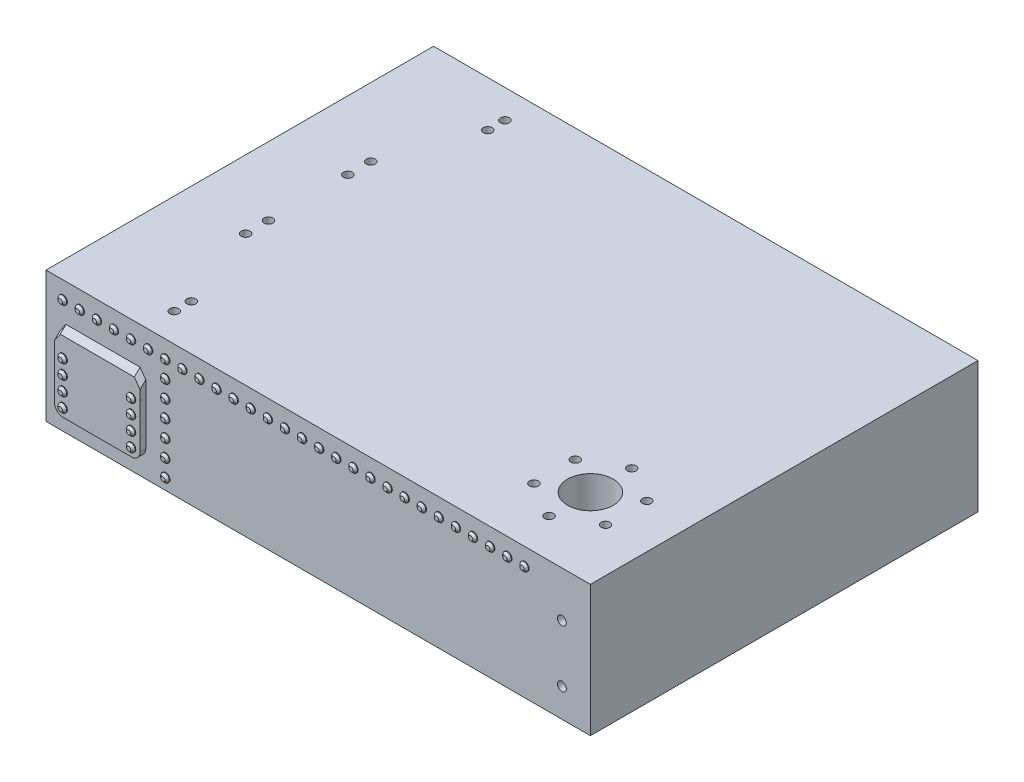
SolidWorks part; units mm, degrees
ref_plane "Front Plane" through (0, 0, 0) normal (0, 0, 1) x (1, 0, 0)
ref_plane "Top Plane" through (0, 0, 0) normal (0, 1, 0) x (1, 0, 0)
ref_plane "Right Plane" through (0, 0, 0) normal (1, 0, 0) x (0, 0, -1)
sketch "Sketch1" plane through (0, 0, 0) normal (0, 1, 0) x (1, 0, 0)
  line L1 (0, 0) -> (191, 0)
  line L2 (0, 0) -> (0, 136)
  line L3 (0, 136) -> (191, 136)
  line L4 (191, 0) -> (191, 136)
  dimension "D1" = 191
  dimension "D2" = 136
extrude "Boss-Extrude1" add sketch "Sketch1" along normal blind 46
sketch "Sketch3" plane through (0, 0, 0) normal (0, -1, 0) x (1, 0, 0)
  line L0 (0, -136) -> (0, 0) construction
  line L1 (5, -5) -> (186, -5)
  line L2 (5, -5) -> (5, -131)
  line L3 (5, -131) -> (186, -131)
  line L4 (186, -5) -> (186, -131)
  line L6 (191, -136) -> (0, -136) construction
  line L7 (191, 0) -> (191, -136) construction
  line L8 (0, 0) -> (191, 0) construction
  dimension "D1" = 5
  dimension "D2" = 5
  dimension "D3" = 5
  dimension "D4" = 5
extrude "Cut-Extrude1" cut sketch "Sketch3" against normal offset from surface (41 mm away) 5 contours L2 L3 L4 L1 up to face at (95.5, 46, -68)
ref_point "FrontLeft"
sketch "Sketch5" plane through (0, 0, -136) normal (0, 0, -1) x (-1, 0, 0)
  line L0 (-191, 46) -> (-119.5, 46)
  line L1 (-191, 46) -> (0, 46) construction
  line L2 (-119.5, 46) -> (-119.5, 0) construction
  line L3 (-191, 0) -> (0, 0) construction
  point P5 (-119.5, 23)
  dimension "D1" = 71.5
sketch "Sketch8" plane through (0, 0, 0) normal (0, 0, 1) x (1, 0, 0)
  line L1 (119.5, 46) -> (119.5, 0) construction
  line L2 (0, 46) -> (191, 46) construction
  line L3 (0, 0) -> (191, 0) construction
  point P0 (119.5, 23)
ref_point "SuspensionMountLeft"
ref_point "SuspensionMountRight"
sketch "Sketch9" plane through (0, 0, -136) normal (0, 0, -1) x (-1, 0, 0)
  line L0 (0, 46) -> (0, 0) construction
  line L1 (-5, 31) -> (-35, 31)
  line L2 (-5, 31) -> (-5, 6.2153)
  line L3 (-5, 6.2153) -> (-35, 6.2153)
  line L4 (-35, 31) -> (-35, 6.2153)
  line L5 (-191, 46) -> (0, 46) construction
  dimension "D1" = 5
  dimension "D2" = 15
  dimension "D3" = 30
extrude "Boss-Extrude2" add sketch "Sketch9" along normal blind 2
chamfer "Chamfer2" distance 2 angle 45 1 edges at (20, 31, -136)
fillet "Fillet1" radius 3 2 edges at (35, 6.2153, -137) (5, 6.2153, -137)
chamfer "Chamfer3" distance 2 angle 45 2 edges at (35, 32, -137) (5, 32, -137)
sketch "Sketch10" plane through (0, 0, 0) normal (0, 0, 1) x (1, 0, 0)
  line L4 (35, 31) -> (5, 31)
  line L5 (35, 6.2153) -> (35, 31)
  line L6 (5, 6.2153) -> (35, 6.2153)
  line L7 (5, 31) -> (5, 6.2153)
  line L8 (35, 31) -> (5, 31)
  line L9 (35, 6.2153) -> (35, 31)
  line L10 (5, 6.2153) -> (35, 6.2153)
  line L11 (5, 31) -> (5, 6.2153)
  dimension "D1" = 0
extrude "Boss-Extrude3" add sketch "Sketch10" along normal blind 2
chamfer "Chamfer4" distance 2 angle 45 1 edges at (20, 31, 0)
fillet "Fillet2" radius 3 2 edges at (35, 6.2153, 1) (5, 6.2153, 1)
chamfer "Chamfer5" distance 2 angle 45 2 edges at (35, 32, 1) (5, 32, 1)
sketch "Sketch23" plane through (0, 0, 2) normal (0, 0, 1) x (1, 0, 0)
  line L0 (8, 9.2153) -> (8, 31) construction
  line L1 (33, 31) -> (7, 31) construction
  line L2 (32, 9.2153) -> (32, 31) construction
  circle A0 centre (8, 9.2153) radius 1.5
  circle A1 centre (32, 9.2153) radius 1.5
  circle A2 centre (8, 14.2153) radius 1.5
  circle A3 centre (32, 14.2153) radius 1.5
  circle A4 centre (8, 19.2153) radius 1.5
  circle A5 centre (32, 19.2153) radius 1.5
  circle A6 centre (8, 24.2153) radius 1.5
  circle A7 centre (32, 24.2153) radius 1.5
  dimension "D1" = 3
  dimension "D2" = 3
  dimension "D3" = 4
extrude "Boss-Extrude8" add sketch "Sketch23" along normal blind 1 contours A4 | A2 | A0 | A1 | A3 | A5 | A7 | A6 region at (8, 9.2153, 2) region at (32, 9.2153, 2) region at (8, 14.2153, 2) region at (32, 14.2153, 2) region at (8, 19.2153, 2) region at (32, 19.2153, 2) region at (32, 24.2153, 2)
chamfer "Chamfer11" distance 0.75 angle 45 8 edges at (9.5, 24.2153, 3) (33.5, 9.2153, 3) (33.5, 14.2153, 3) (33.5, 19.2153, 3) (33.5, 24.2153, 3) (9.5, 9.2153, 3) (9.5, 14.2153, 3) (9.5, 19.2153, 3)
ref_plane "Plane1" through (0, 0, -68) normal (0, 0, 1) x (1, 0, 0)
mirror "Mirror1" about plane through (0, 0, -68) normal (0, 0, 1) of "Chamfer11", "Boss-Extrude8"
sketch "Sketch18" plane through (0, 41, 0) normal (0, -1, 0) x (1, 0, 0)
  line L1 (112.6585, -114) -> (114.6793, -117.5)
  line L2 (114.6793, -117.5) -> (118.7207, -117.5)
  line L3 (118.7207, -117.5) -> (120.7415, -114)
  line L4 (120.7415, -114) -> (118.7207, -110.5)
  line L5 (118.7207, -110.5) -> (114.6793, -110.5)
  line L6 (114.6793, -110.5) -> (112.6585, -114)
  line L7 (112.6585, -66) -> (114.6793, -69.5)
  line L8 (114.6793, -69.5) -> (118.7207, -69.5)
  line L9 (118.7207, -69.5) -> (120.7415, -66)
  line L10 (120.7415, -66) -> (118.7207, -62.5)
  line L11 (118.7207, -62.5) -> (114.6793, -62.5)
  line L12 (114.6793, -62.5) -> (112.6585, -66)
  line L13 (12.4585, -67) -> (14.4793, -70.5)
  line L14 (14.4793, -70.5) -> (18.5207, -70.5)
  line L15 (18.5207, -70.5) -> (20.5415, -67)
  line L16 (20.5415, -67) -> (18.5207, -63.5)
  line L17 (18.5207, -63.5) -> (14.4793, -63.5)
  line L18 (14.4793, -63.5) -> (12.4585, -67)
  line L19 (12.4585, -119.5) -> (14.4793, -123)
  line L20 (14.4793, -123) -> (18.5207, -123)
  line L21 (18.5207, -123) -> (20.5415, -119.5)
  line L22 (20.5415, -119.5) -> (18.5207, -116)
  line L23 (18.5207, -116) -> (14.4793, -116)
  line L24 (14.4793, -116) -> (12.4585, -119.5)
  circle A0 centre (116.7, -114) radius 3.5 construction
  circle A9 centre (116.7, -66) radius 3.5 construction
  circle A10 centre (16.5, -67) radius 3.5 construction
  circle A11 centre (16.5, -119.5) radius 3.5 construction
  point P41 (116.7, -114)
  point P42 (116.7, -66)
  point P43 (16.5, -67)
  point P44 (16.5, -119.5)
extrude "Boss-Extrude7" add sketch "Sketch18" along normal blind 14
sketch "Sketch19" plane through (0, 27, 0) normal (0, -1, 0) x (1, 0, 0)
  line L6 (112.6585, -66) -> (114.6793, -69.5)
  line L7 (114.6793, -69.5) -> (118.7207, -69.5)
  line L8 (118.7207, -69.5) -> (120.7415, -66)
  line L9 (120.7415, -66) -> (118.7207, -62.5)
  line L10 (118.7207, -62.5) -> (114.6793, -62.5)
  line L11 (114.6793, -62.5) -> (112.6585, -66)
  line L12 (112.6585, -66) -> (114.6793, -69.5)
  line L13 (114.6793, -69.5) -> (118.7207, -69.5)
  line L14 (118.7207, -69.5) -> (120.7415, -66)
  line L15 (120.7415, -66) -> (118.7207, -62.5)
  line L16 (118.7207, -62.5) -> (114.6793, -62.5)
  line L17 (114.6793, -62.5) -> (112.6585, -66)
  line L18 (120.7415, -114) -> (118.7207, -110.5)
  line L19 (118.7207, -110.5) -> (114.6793, -110.5)
  line L20 (114.6793, -110.5) -> (112.6585, -114)
  line L21 (112.6585, -114) -> (114.6793, -117.5)
  line L22 (114.6793, -117.5) -> (118.7207, -117.5)
  line L23 (118.7207, -117.5) -> (120.7415, -114)
  line L24 (120.7415, -114) -> (118.7207, -110.5)
  line L25 (118.7207, -110.5) -> (114.6793, -110.5)
  line L26 (114.6793, -110.5) -> (112.6585, -114)
  line L27 (112.6585, -114) -> (114.6793, -117.5)
  line L28 (114.6793, -117.5) -> (118.7207, -117.5)
  line L29 (118.7207, -117.5) -> (120.7415, -114)
  line L30 (12.4585, -119.5) -> (14.4793, -123)
  line L31 (14.4793, -123) -> (18.5207, -123)
  line L32 (18.5207, -123) -> (20.5415, -119.5)
  line L33 (20.5415, -119.5) -> (18.5207, -116)
  line L34 (18.5207, -116) -> (14.4793, -116)
  line L35 (14.4793, -116) -> (12.4585, -119.5)
  line L36 (12.4585, -119.5) -> (14.4793, -123)
  line L37 (14.4793, -123) -> (18.5207, -123)
  line L38 (18.5207, -123) -> (20.5415, -119.5)
  line L39 (20.5415, -119.5) -> (18.5207, -116)
  line L40 (18.5207, -116) -> (14.4793, -116)
  line L41 (14.4793, -116) -> (12.4585, -119.5)
  line L42 (18.5207, -63.5) -> (14.4793, -63.5)
  line L43 (20.5415, -67) -> (18.5207, -63.5)
  line L44 (18.5207, -70.5) -> (20.5415, -67)
  line L45 (14.4793, -70.5) -> (18.5207, -70.5)
  line L46 (12.4585, -67) -> (14.4793, -70.5)
  line L47 (14.4793, -63.5) -> (12.4585, -67)
  line L48 (18.5207, -63.5) -> (14.4793, -63.5)
  line L49 (20.5415, -67) -> (18.5207, -63.5)
  line L50 (18.5207, -70.5) -> (20.5415, -67)
  line L51 (14.4793, -70.5) -> (18.5207, -70.5)
  line L52 (12.4585, -67) -> (14.4793, -70.5)
  line L53 (14.4793, -63.5) -> (12.4585, -67)
  circle A0 centre (116.7, -66) radius 4.0415
  circle A1 centre (16.5, -67) radius 4.0415
  circle A2 centre (16.5, -119.5) radius 4.0415
  circle A3 centre (116.7, -114) radius 4.0415
  dimension "D1" = 0
  dimension "D2" = 0
  dimension "D3" = 0
  dimension "D4" = 0
hole_wizard "CSK for M2 Flat Head Machine Screw1" positions "Sketch21" profile "Sketch20" countersink size "M2" standard "ANSI Metric"
sketch "Sketch21" plane through (0, 27, 0) normal (0, -1, 0) x (-1, 0, 0)
  point P0 (-116.7, 114)
  point P3 (-116.7, 66)
  point P6 (-16.5, 67)
  point P9 (-16.5, 119.5)
sketch "Sketch20" plane through (116.7, 27, -114) normal (1, 0, 0) x (0, 0, -1)
  line L0 (0, 0) -> (0, 13.6009)
  line L1 (0, 13.6009) -> (1, 13)
  line L2 (1, 13) -> (1, 0.4195)
  line L3 (1, 0.4195) -> (1.5, 0)
  line L5 (1.5, 0) -> (0, 0)
  line L6 (-1, 0.4195) -> (-1.5, 0) construction
  line L10 (0, 13.6009) -> (-1, 13) construction
  line L11 (0, -6.35) -> (0, 107.95) construction
  dimension "Hole Dia." = 2
  dimension "Hole Depth" = 13
  dimension "Near C'Sink Dia." = 3
  dimension "Near C'Sink Angle" = 100
  dimension "Drill Angle" = 118
sketch "Sketch22" plane through (0, 0, 0) normal (-1, 0, 0) x (0, 0, 1)
  line L0 (0, 46) -> (0, 0) construction
  line L1 (-10, 10) -> (-80, 10)
  line L2 (-10, 10) -> (-10, 38)
  line L3 (-10, 38) -> (-80, 38)
  line L4 (-80, 10) -> (-80, 38)
  line L5 (-136, 0) -> (0, 0) construction
  line L6 (-136, 46) -> (0, 46) construction
  dimension "D1" = 10
  dimension "D2" = 10
  dimension "D3" = 8
  dimension "D4" = 70
extrude "Cut-Extrude2" [suppressed] cut sketch "Sketch22" against normal up to next
chamfer "Chamfer10" [suppressed] distance 28 angle 45
fillet "Fillet3" [suppressed] radius 3
sketch "Sketch24" plane through (0, 0, 0) normal (0, 0, 1) x (1, 0, 0)
  line L0 (0, 40) -> (191, 40) construction
  line L1 (0, 46) -> (0, 0) construction
  line L2 (191, 46) -> (191, 0) construction
  line L3 (0, 46) -> (191, 46) construction
  circle A0 centre (6, 40) radius 1.5
  circle A1 centre (12, 40) radius 1.5
  circle A2 centre (18, 40) radius 1.5
  circle A3 centre (24, 40) radius 1.5
  circle A4 centre (30, 40) radius 1.5
  circle A5 centre (36, 40) radius 1.5
  circle A6 centre (42, 40) radius 1.5
  circle A7 centre (48, 40) radius 1.5
  circle A8 centre (54, 40) radius 1.5
  circle A9 centre (60, 40) radius 1.5
  circle A10 centre (66, 40) radius 1.5
  circle A11 centre (72, 40) radius 1.5
  circle A12 centre (78, 40) radius 1.5
  circle A13 centre (84, 40) radius 1.5
  circle A14 centre (90, 40) radius 1.5
  circle A15 centre (96, 40) radius 1.5
  circle A16 centre (102, 40) radius 1.5
  circle A17 centre (108, 40) radius 1.5
  circle A18 centre (114, 40) radius 1.5
  circle A19 centre (120, 40) radius 1.5
  circle A20 centre (126, 40) radius 1.5
  circle A21 centre (132, 40) radius 1.5
  circle A22 centre (138, 40) radius 1.5
  circle A23 centre (144, 40) radius 1.5
  circle A24 centre (150, 40) radius 1.5
  circle A25 centre (156, 40) radius 1.5
  circle A26 centre (162, 40) radius 1.5
  circle A27 centre (168, 40) radius 1.5
  circle A28 centre (42, 34) radius 1.5
  circle A29 centre (42, 28) radius 1.5
  circle A30 centre (42, 22) radius 1.5
  circle A31 centre (42, 16) radius 1.5
  circle A32 centre (42, 10) radius 1.5
  circle A33 centre (42, 4) radius 1.5
  dimension "D2" = 3
  dimension "D1" = 6
  dimension "D3" = 6
  dimension "D4" = 28
  dimension "D5" = 7
extrude "Boss-Extrude9" add sketch "Sketch24" along normal blind 1
chamfer "Chamfer12" distance 0.75 angle 45 34 edges at (169.5, 40, 1) (163.5, 40, 1) (157.5, 40, 1) (151.5, 40, 1) (145.5, 40, 1) (139.5, 40, 1) (133.5, 40, 1) (127.5, 40, 1) (121.5, 40, 1) (115.5, 40, 1) (109.5, 40, 1) (103.5, 40, 1) (97.5, 40, 1) (91.5, 40, 1) (85.5, 40, 1) (79.5, 40, 1) (73.5, 40, 1) (67.5, 40, 1) (43.5, 4, 1) (43.5, 10, 1) (43.5, 16, 1) (43.5, 22, 1) (43.5, 28, 1) (43.5, 34, 1) (61.5, 40, 1) (55.5, 40, 1) (49.5, 40, 1) (43.5, 40, 1) (37.5, 40, 1) (31.5, 40, 1) (25.5, 40, 1) (19.5, 40, 1) (13.5, 40, 1) (7.5, 40, 1)
mirror "Mirror3" about plane through (0, 0, -68) normal (0, 0, 1) of "Chamfer12", "Boss-Extrude9"
sketch "Sketch25" plane through (0, 0, -131) normal (0, 0, 1) x (1, 0, 0)
  circle A0 centre (181, 30) radius 1.55 construction
  circle A1 centre (181, 10) radius 1.55 construction
  circle A2 centre (181, 30) radius 1.55
  circle A3 centre (181, 10) radius 1.55
extrude "Cut-Extrude3" cut sketch "Sketch25" against normal through all
sketch "Sketch26" plane through (0, 0, -5) normal (0, 0, -1) x (-1, 0, 0)
  circle A1 centre (-181, 10) radius 1.55
  circle A2 centre (-181, 10) radius 1.55
  circle A3 centre (-181, 30) radius 1.55
  circle A4 centre (-181, 30) radius 1.55
  dimension "D1" = 0
  dimension "D2" = 0
extrude "Cut-Extrude4" cut sketch "Sketch26" against normal through all
sketch "Sketch27" plane through (0, 46, 0) normal (0, 1, 0) x (1, 0, 0)
  line L0 (191, 0) -> (191, 136) construction
  line L1 (0, 0) -> (191, 0) construction
  circle A0 centre (163, 28) radius 1
  dimension "D1" = 2
  dimension "D2" = 28
  dimension "D3" = 28
sketch "Sketch28" plane through (0, 41, 0) normal (0, -1, 0) x (1, 0, 0)
  circle A0 centre (163, -13.5) radius 1.55 construction
  circle A1 centre (163, -28) radius 18
  circle A2 centre (163, -28) radius 18
  circle A3 centre (163, -28) radius 8
  circle A4 centre (163, -28) radius 8
  circle A5 centre (175.5574, -20.75) radius 1.55 construction
  circle A6 centre (175.5574, -35.25) radius 1.55 construction
  circle A7 centre (163, -42.5) radius 1.55 construction
  circle A8 centre (150.4426, -35.25) radius 1.55 construction
  circle A9 centre (150.4426, -20.75) radius 1.55 construction
  circle A10 centre (163, -13.5) radius 1.55
  circle A11 centre (175.5574, -20.75) radius 1.55
  circle A12 centre (175.5574, -35.25) radius 1.55
  circle A13 centre (163, -42.5) radius 1.55
  circle A14 centre (150.4426, -35.25) radius 1.55
  circle A15 centre (150.4426, -20.75) radius 1.55
  circle A17 centre (163, -28) radius 11
  circle A18 centre (163, -28) radius 11
  dimension "D1" = 0
  dimension "D2" = 0
  dimension "D3" = 0
extrude "Cut-Extrude5" cut sketch "Sketch28" against normal through all contours A13 | A12 | A11 | A10 | A15 | A14 region at (163, 41, -13.5) region at (175.5574, 41, -20.75) region at (175.5574, 41, -35.25) region at (163, 41, -42.5) region at (150.4426, 41, -35.25) region at (150.4426, 41, -20.75)
extrude "Cut-Extrude6" cut sketch "Sketch28<3>" against normal through all contours A4 region at (163, 41, -28)
sketch "Sketch28<3>" plane through (0, 41, 0) normal (0, -1, 0) x (1, 0, 0) same geometry as "Sketch28"
extrude "Boss-Extrude10" add sketch "Sketch28<4>" along normal blind 40 contours A18 A4 region at (152.3111, 41, -28)
sketch "Sketch28<4>" plane through (0, 41, 0) normal (0, -1, 0) x (1, 0, 0) same geometry as "Sketch28"
sketch "Sketch29" plane through (0, 1, 0) normal (0, -1, 0) x (1, 0, 0)
  line L0 (163, -28) -> (163, -43.0058) construction
  line L1 (163, -43.0058) -> (162, -43.0058)
  line L2 (163, -43.0058) -> (164, -43.0058)
  line L3 (164, -43.0058) -> (164, -13.0058)
  line L4 (164, -13.0058) -> (162, -13.0058)
  line L5 (162, -13.0058) -> (162, -43.0058)
  dimension "D2" = 1
  dimension "D1" = 1
  dimension "D3" = 30
extrude "Cut-Extrude7" cut sketch "Sketch29" against normal blind 20
ref_plane "Plane2" through (163, 46, -28) normal (0, 0, 1) x (1, 0, 0)
sketch "Sketch30" plane through (163, 46, -28) normal (0, 0, 1) x (1, 0, 0)
  line L0 (11, -5) -> (11, -46) construction
  line L1 (11, -45) -> (11, -5) construction
  line L2 (18, -5) -> (18, -46) construction
  line L3 (18, -5) -> (11, -25.5) construction
  line L4 (23, -5) -> (-158, -5)
  line L5 (-158, -5) -> (-158, -46)
  line L6 (-158, -46) -> (23, -46)
  line L7 (23, -46) -> (23, -5)
  line L8 (23, -5) -> (-158, -5)
  line L9 (-158, -5) -> (-158, -46)
  line L10 (-158, -46) -> (23, -46)
  line L11 (23, -46) -> (23, -5)
  line L12 (17, -7.9286) -> (12, -22.5714)
  line L13 (17, -7.9286) -> (17, -5)
  line L14 (17, -5) -> (17, -4.9)
  line L15 (12, -22.5714) -> (11, -22.5714)
  line L16 (11, -22.5714) -> (10.9, -22.5714)
  line L17 (10.9, -22.5714) -> (10.9, -4.9)
  line L18 (10.9, -4.9) -> (17, -4.9)
  dimension "D2" = 1
  dimension "D3" = 1
  dimension "D4" = 0.1
  dimension "D5" = 0.1
  dimension "D1" = 0
extrude "Boss-Extrude11" add sketch "Sketch30" along normal mid plane 3 contours L17 L16 L15 L12 L13 L8 region at (176.2325, 34.2396, -28)
ref_axis "Axis1" through (163, 46, -28) along (0, -1, 0)
pattern_circular "CirPattern1" count 6 over 360 about axis through (163, 46, -28) along (0, -1, 0) of "Boss-Extrude11"
chamfer "Chamfer13" distance 0.5 angle 45 2 edges at (174, 1, -28) (152, 1, -28)
sketch "Sketch31" plane through (0, 41, 0) normal (0, -1, 0) x (1, 0, 0)
  circle A0 centre (35, -16) radius 1.55 construction
  circle A1 centre (35, -10) radius 1.55 construction
  circle A2 centre (35, -126) radius 1.55 construction
  circle A3 centre (35, -120) radius 1.55 construction
  circle A4 centre (35, -16) radius 1.55
  circle A5 centre (35, -10) radius 1.55
  circle A6 centre (35, -126) radius 1.55
  circle A7 centre (35, -120) radius 1.55
extrude "Cut-Extrude8" cut sketch "Sketch31" against normal up to next
sketch "Sketch32" plane through (5, 0, 0) normal (1, 0, 0) x (0, 0, -1)
  circle A0 centre (125.5, 17.25) radius 1.55 construction
  circle A1 centre (10.5, 17.25) radius 1.55 construction
  circle A2 centre (125.5, 17.25) radius 1.55
  circle A3 centre (10.5, 17.25) radius 1.55
extrude "Cut-Extrude9" cut sketch "Sketch32" against normal up to next
sketch "Sketch34" plane through (5, 0, 0) normal (1, 0, 0) x (0, 0, -1)
  circle A0 centre (46.0692, 8) radius 1.55 construction
  circle A1 centre (89.9308, 8) radius 1.55 construction
  circle A2 centre (46.0692, 8) radius 1.55
  circle A3 centre (89.9308, 8) radius 1.55
extrude "Cut-Extrude10" cut sketch "Sketch34" against normal up to next
sketch "Sketch35" plane through (0, 41, 0) normal (0, -1, 0) x (1, 0, 0)
  circle A0 centre (24, -46.0692) radius 1.55 construction
  circle A1 centre (24, -54.0692) radius 1.55 construction
  circle A2 centre (24, -81.9308) radius 1.55 construction
  circle A3 centre (24, -89.9308) radius 1.55 construction
  circle A4 centre (24, -46.0692) radius 1.55
  circle A5 centre (24, -54.0692) radius 1.55
  circle A6 centre (24, -81.9308) radius 1.55
  circle A7 centre (24, -89.9308) radius 1.55
extrude "Cut-Extrude11" cut sketch "Sketch35" against normal up to next
sketch "Sketch36" plane through (0, 46, 0) normal (0, 1, 0) x (1, 0, 0)
  line L0 (191, 68) -> (85, 68) construction
  line L1 (191, 0) -> (191, 136) construction
  dimension "D1" = 106
sketch "Sketch37" plane through (0, 0, 0) normal (0, -1, 0) x (1, 0, 0)
  line L4 (0, -136) -> (142.2, -136)
  line L5 (0, 0) -> (0, -136)
  line L6 (142.2, 0) -> (0, 0)
  line L7 (142.2, -136) -> (142.2, 0)
  line L8 (0, -136) -> (142.2, -136)
  line L9 (0, 0) -> (0, -136)
  line L10 (142.2, 0) -> (0, 0)
  line L11 (142.2, -136) -> (142.2, 0)
  arc A0 (8, -131) -> (5, -128) centre (5, -131) ccw construction
  arc A1 (5, -8) -> (8, -5) centre (5, -5) ccw construction
  arc A2 (134.2, -5) -> (137.2, -8) centre (137.2, -5) ccw construction
  arc A3 (137.2, -128) -> (134.2, -131) centre (137.2, -131) ccw construction
  arc A4 (8, -131) -> (5, -128) centre (5, -131) ccw
  arc A5 (5, -8) -> (8, -5) centre (5, -5) ccw
  arc A6 (134.2, -5) -> (137.2, -8) centre (137.2, -5) ccw
  arc A7 (137.2, -128) -> (134.2, -131) centre (137.2, -131) ccw
  circle A8 centre (5, -131) radius 3
  circle A9 centre (5, -5) radius 3
  circle A10 centre (137.2, -5) radius 3
  circle A11 centre (137.2, -131) radius 3
  line M9 (5, -131) -> (5, -5)
  line M10 (5, -5) -> (186, -5)
  line M12 (186, -131) -> (5, -131)
  dimension "D1" = 0
extrude "Boss-Extrude12" add sketch "Sketch37" against normal blind 12 contours A11 A7 M12 | A6 A10 M10 | A5 M9 M10 | A4 M12 M9 region at (137.2, 0, -129.7268) region at (137.2, 0, -6.2732) region at (6.2732, 0, -129.7268) region at (6.2732, 0, -6.2732)
chamfer "Chamfer14" distance 2.999 angle 45 4 edges at (7.1213, 12, -128.8787) (137.2, 12, -128) (137.2, 12, -8) (7.1213, 12, -7.1213)
sketch "Sketch38" plane through (0, 0, 0) normal (0, -1, 0) x (1, 0, 0)
  circle A0 centre (137.2, -131) radius 1.55
  circle A1 centre (137.2, -5) radius 1.55
  circle A2 centre (5, -5) radius 1.55
  circle A3 centre (5, -131) radius 1.55
  dimension "D1" = 3.1
  dimension "D2" = 3.1
  dimension "D3" = 3.1
  dimension "D4" = 3.1
extrude "Cut-Extrude12" cut sketch "Sketch38" against normal blind 2
